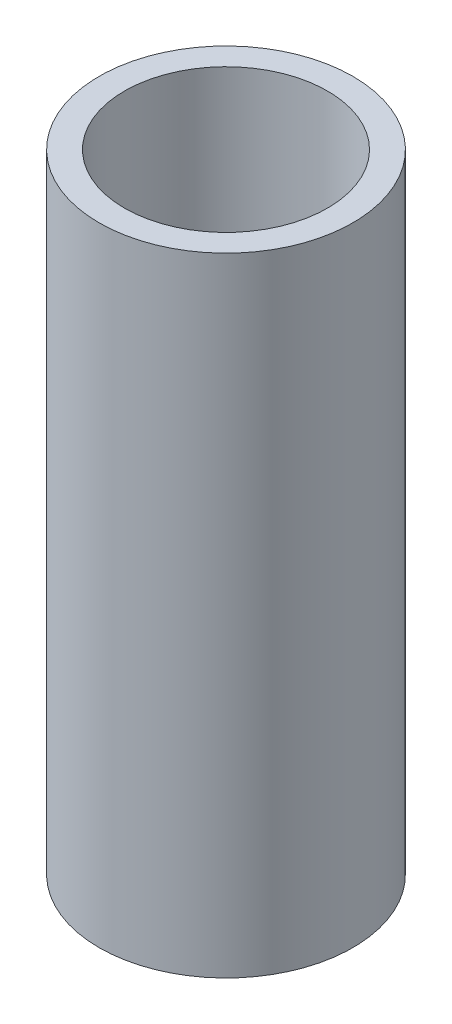
SolidWorks part; units mm, degrees
ref_plane "Front Plane" through (0, 0, 0) normal (0, 0, 1) x (1, 0, 0)
ref_plane "Top Plane" through (0, 0, 0) normal (0, 1, 0) x (1, 0, 0)
ref_plane "Right Plane" through (0, 0, 0) normal (1, 0, 0) x (0, 0, -1)
ref_plane "Plane1" through (0, 0, 0) normal (0, 0, 1) x (1, 0, 0)
sketch "Sketch1" plane through (0, 0, 0) normal (0, 0, 1) x (1, 0, 0)
  line L0 (1.52, 9.4) -> (1.52, 0)
  line L1 (1.52, 0) -> (1.9, 0)
  line L2 (1.9, 0) -> (1.9, 9.4)
  line L3 (1.9, 9.4) -> (1.52, 9.4)
  line L4 (0, 0) -> (0, 9.4) construction
revolve "Revolve1" add sketch "Sketch1" angle 360 about L4 reverse direction yes
